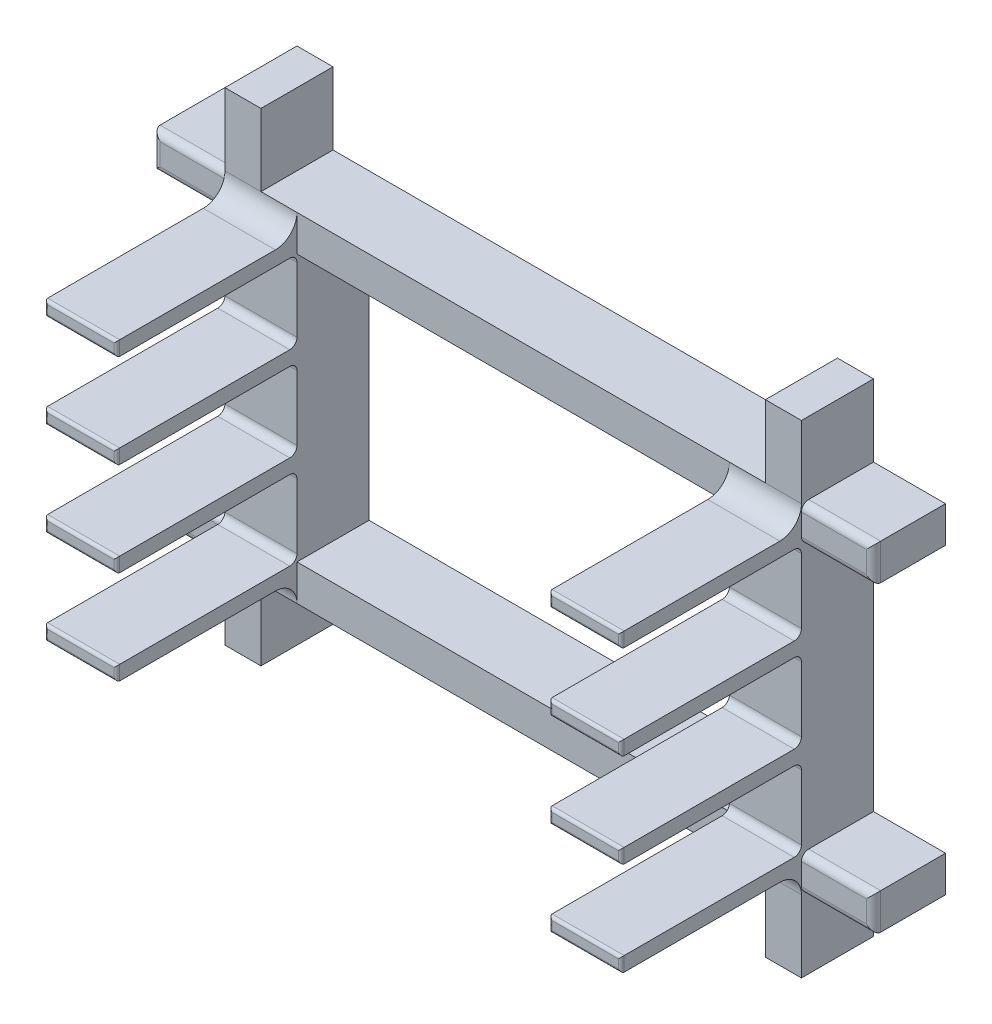
SolidWorks part; units mm, degrees
ref_plane "Ön Düzlem" through (0, 0, 0) normal (1, 0, 0) x (0, 1, 0)
ref_plane "Üst Düzlem" through (0, 0, 0) normal (0, 0, 1) x (0, 1, 0)
ref_plane "Sağ Düzlem" through (0, 0, 0) normal (0, 1, 0) x (-1, 0, 0)
sketch "Sketch1" plane through (0, 0, 0) normal (0, 0, 1) x (0, 1, 0)
  line L0 (0, 10) -> (0, -90)
  line L3 (0, -10) -> (-37, -10)
  line L7 (-37, -90) -> (-42, -90)
  line L11 (0, 10) -> (5, 10)
  line L15 (0, -90) -> (5, -90)
  line L19 (-37, 10) -> (-42, 10)
  line L21 (-26, -10) -> (-26, 0)
  line L22 (-13, -10) -> (-13, 0)
  line L23 (-24, -10) -> (-24, 0)
  line L24 (-11, -10) -> (-11, 0)
  line L25 (5, 10) -> (5, -90)
  line L26 (-37, -80) -> (0, -80)
  line L28 (-37, -70) -> (0, -70)
  line L30 (-42, -90) -> (-42, 10)
  line L31 (-37, -90) -> (-37, 10)
  line L32 (-37, 0) -> (0, 0)
  line L33 (-26, -70) -> (-26, -80)
  line L34 (-24, -70) -> (-24, -80)
  line L35 (-13, -70) -> (-13, -80)
  line L36 (-11, -70) -> (-11, -80)
  dimension "D1" = 5
  dimension "D2" = 100
  dimension "D3" = 5
  dimension "D4" = 10
  dimension "D5" = 2
  dimension "D6" = 2
  dimension "D7" = 11
  dimension "D8" = 10
  dimension "D9" = 60
  dimension "D10" = 11
  dimension "D11" = 11
  dimension "D12" = 10
sketch "Sketch2" plane through (0, 0, 0) normal (0, 0, 1) x (0, 1, 0)
  line L0 (-42, 10) -> (-42, 0)
  line L1 (-42, -90) -> (-37, -90)
  line L2 (-37, -90) -> (-37, -80)
  line L3 (-37, -80) -> (0, -80)
  line L4 (0, -80) -> (0, -90)
  line L5 (0, -90) -> (5, -90)
  line L6 (5, -90) -> (5, -80)
  line L7 (5, 10) -> (0, 10)
  line L8 (0, 10) -> (0, 0)
  line L9 (0, 0) -> (-37, 0)
  line L10 (-37, 0) -> (-37, 10)
  line L11 (-37, 10) -> (-42, 10)
  line L12 (-37, -10) -> (0, -10)
  line L13 (0, -10) -> (0, -70)
  line L14 (0, -70) -> (-37, -70)
  line L15 (-37, -70) -> (-37, -10)
  line L16 (-42, 0) -> (-52, 0)
  line L17 (-52, 0) -> (-52, -5)
  line L18 (-52, -5) -> (-42, -5)
  line L19 (5, 0) -> (15, 0)
  line L20 (15, 0) -> (15, -5)
  line L21 (15, -5) -> (5, -5)
  line L22 (5, -75) -> (15, -75)
  line L23 (15, -75) -> (15, -80)
  line L24 (15, -80) -> (5, -80)
  line L25 (-42, -80) -> (-52, -80)
  line L26 (-52, -80) -> (-52, -75)
  line L27 (-52, -75) -> (-42, -75)
  line L28 (-42, -5) -> (-42, -75)
  line L29 (5, -75) -> (5, -5)
  line L30 (-42, -80) -> (-42, -90)
  line L31 (5, 0) -> (5, 10)
extrude "Boss-Extrude1" add sketch "Sketch2" along normal blind 10
sketch "Sketch3" plane through (0, 0, 10) normal (0, 0, 1) x (1, 0, 0)
  line L0 (0, 0) -> (0, 2)
  line L1 (0, 2) -> (10, 2)
  line L2 (10, 2) -> (10, 0)
  line L3 (0, 0) -> (10, 0)
  line L4 (10, -11) -> (10, -13)
  line L5 (10, -13) -> (0, -13)
  line L6 (0, -13) -> (0, -11)
  line L7 (0, -11) -> (10, -11)
  line L8 (10, -24) -> (10, -26)
  line L9 (10, -26) -> (0, -26)
  line L10 (0, -26) -> (0, -24)
  line L11 (0, -24) -> (10, -24)
  line L12 (10, -37) -> (10, -39)
  line L13 (10, -39) -> (0, -39)
  line L14 (0, -39) -> (0, -37)
  line L15 (0, -37) -> (10, -37)
  line L16 (70, 0) -> (70, 2)
  line L17 (70, 2) -> (80, 2)
  line L18 (80, 2) -> (80, 0)
  line L19 (80, 0) -> (70, 0)
  line L20 (70, -11) -> (70, -13)
  line L21 (70, -13) -> (80, -13)
  line L22 (80, -13) -> (80, -11)
  line L23 (80, -11) -> (70, -11)
  line L24 (70, -24) -> (70, -26)
  line L25 (70, -26) -> (80, -26)
  line L26 (80, -26) -> (80, -24)
  line L27 (80, -24) -> (70, -24)
  line L28 (70, -37) -> (70, -39)
  line L29 (70, -39) -> (80, -39)
  line L30 (80, -39) -> (80, -37)
  line L31 (80, -37) -> (70, -37)
extrude "Boss-Extrude2" add sketch "Sketch3" along normal blind 25
fillet "Fillet1" radius 3 2 edges at (75, -39, 10) (5, -39, 10)
fillet "Fillet2" radius 3 2 edges at (75, 2, 10) (5, 2, 10)
fillet "Fillet3" radius 1 12 edges at (75, -11, 10) (75, -24, 10) (75, -37, 10) (75, -26, 10) (75, -13, 10) (75, 0, 10) (5, 0, 10) (5, -11, 10) (5, -13, 10) (5, -24, 10) (5, -26, 10) (5, -37, 10)
fillet "Fillet6" radius 1 3 edges at (-5, -37, 10) (-10, -39.5, 10) (-5, -42, 10)
fillet "Fillet7" radius 1 3 edges at (-5, 5, 10) (-10, 2.5, 10) (-5, 0, 10)
fillet "Fillet8" radius 1 3 edges at (85, 5, 10) (90, 2.5, 10) (85, 0, 10)
fillet "Fillet9" radius 1 3 edges at (85, -37, 10) (90, -39.5, 10) (85, -42, 10)
fillet "Fillet10" radius 0.4 32 edges at (0, 1, 35) (5, 0, 35) (10, 1, 35) (5, 2, 35) (0, -12, 35) (5, -13, 35) (10, -12, 35) (5, -11, 35) (0, -25, 35) (5, -26, 35) (10, -25, 35) (5, -24, 35) (0, -38, 35) (5, -39, 35) (10, -38, 35) (5, -37, 35) (70, 1, 35) (75, 0, 35) (80, 1, 35) (75, 2, 35) (70, -12, 35) (75, -13, 35) (80, -12, 35) (75, -11, 35) (70, -25, 35) (75, -26, 35) (80, -25, 35) (75, -24, 35) (70, -38, 35) (75, -39, 35) (80, -38, 35) (75, -37, 35)
